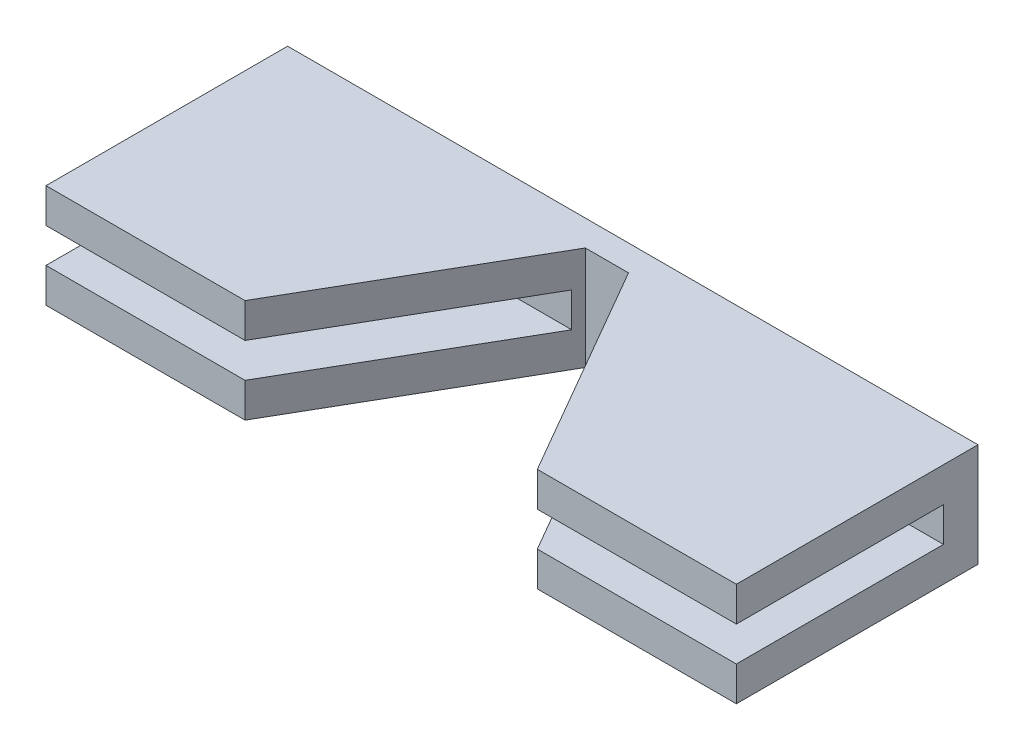
SolidWorks part; units mm, degrees
ref_plane "Front Plane" through (0, 0, 0) normal (0, 0, 1) x (1, 0, 0)
ref_plane "Top Plane" through (0, 0, 0) normal (0, 1, 0) x (1, 0, 0)
ref_plane "Right Plane" through (0, 0, 0) normal (1, 0, 0) x (0, 0, -1)
sketch "Sketch1" plane through (0, 0, 0) normal (0, 1, 0) x (1, 0, 0)
  line L0 (0, 0) -> (0, -14)
  line L1 (0, -14) -> (11.5331, -14)
  line L3 (20, 0) -> (0, 0)
  line L4 (11.5331, -14) -> (18.75, -1.5)
  line L5 (18.75, -1.5) -> (20, -1.5)
  line L9 (20, -1.5) -> (20, 0)
  dimension "D1" = 20
  dimension "D2" = 14
  dimension "D5" = 60
  dimension "D6" = 1.25
  dimension "D7" = 1.5
extrude "Boss-Extrude1" add sketch "Sketch1" along normal blind 6
shell "Shell2" thickness 2 removed face at (15.1416, 3, 7.75) removed face at (5.7666, 3, 14) removed face at (0, 3, 7)
ref_plane "Plane1" through (20, 0, 0) normal (1, 0, 0) x (0, 0, -1)
mirror "Mirror1" about plane through (20, 0, 0) normal (1, 0, 0) of bodies 101
equation "\"fin_thickness\"= 3mm'Exact"
equation "\"D1@Boss-Extrude1\"=\"fin_thickness\"+3mm"
